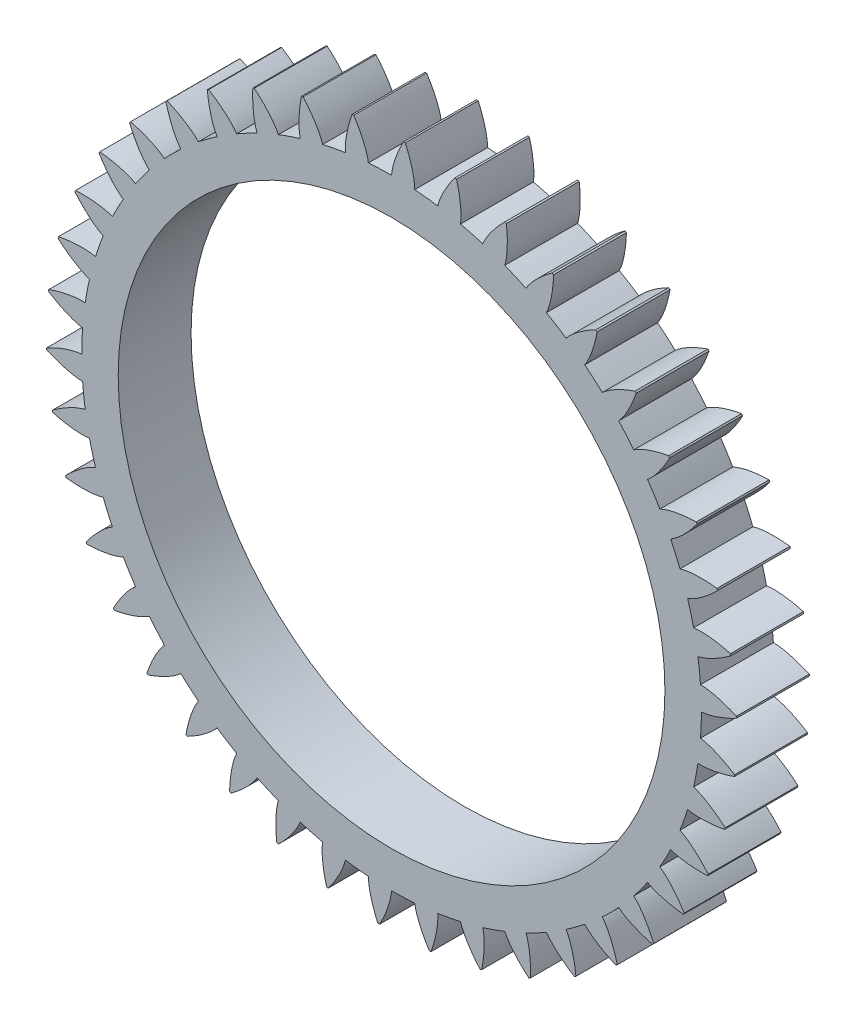
SolidWorks part; units mm, degrees
ref_plane "Front Plane" through (0, 0, 0) normal (0, 0, 1) x (1, 0, 0)
ref_plane "Top Plane" through (0, 0, 0) normal (0, 1, 0) x (1, 0, 0)
ref_plane "Right Plane" through (0, 0, 0) normal (1, 0, 0) x (0, 0, -1)
sketch "Sketch1" plane through (0, 0, 0) normal (0, 0, 1) x (1, 0, 0)
  line L0 (0, 0) -> (47.3193, -1.7706) construction
  line L1 (0, 0) -> (47.3193, 1.7706) construction
  line L2 (0, 0) -> (47.3193, -1.7706) construction
  line L3 (0, 0) -> (47.3524, 0) construction
  line L4 (0, 0) -> (47.0546, 5.3018) construction
  line L5 (0, 0) -> (47.3193, 1.7706)
  line L6 (42.4798, -1.5895) -> (37.4833, -1.4025)
  circle A0 centre (0, 0) radius 45.2 construction
  circle A1 centre (0, 0) radius 42.5095 construction
  circle A2 centre (0, 0) radius 42.4741 construction
  circle A3 centre (0, 0) radius 47.3524 construction
  arc A4 (42.5059, 0.5579) -> (42.4798, -1.5895) centre (0, 0) cw
  arc A5 (47.2632, 2.9041) -> (47.0335, -5.4865) centre (0, 0) cw
  arc A6 (37.4833, -1.4025) -> (37.4833, 1.4025) centre (0, 0) ccw
  spline S0 degree 4 poles (42.4741, 0) (42.5302, 0.0017) (42.6422, 0.0081) (42.9552, 0.0423) (43.546, 0.1494) (44.436, 0.3854) (45.6255, 0.8173) (47.1022, 1.5003) (48.755, 2.4501) (50.4757, 3.6438) (52.2195, 5.0775) (53.8537, 6.6343) (55.3803, 8.2963) (56.8717, 10.1359) (58.5748, 12.5231) (60.3856, 15.5166) (62.1816, 19.1625) (63.799, 23.3792) (65.0524, 27.7173) (65.9558, 32.1409) (66.5234, 36.6196) (66.7382, 40.5636) (66.7293, 43.9479) (66.5972, 46.7643) (66.4185, 49.0128) (66.1681, 51.2546) (65.8479, 53.487) (65.4591, 55.7094) (65.0607, 57.6414) (64.6778, 59.2907) (64.3799, 60.4692) (64.1876, 61.1947) (64.0217, 61.8024) (63.8414, 62.4443) (63.6884, 62.9728) (63.3886, 63.9768) (63.1489, 64.7323) (62.847, 65.6664) (62.5677, 66.4852) (62.2579, 67.3724) (61.953, 68.206) (61.7078, 68.8614) (61.5473, 69.276) (61.4636, 69.4921) knots 0 0 0 0 0 0.002802 0.005604 0.015718 0.02996 0.048734 0.068727 0.096889 0.125051 0.153212 0.181374 0.209535 0.237696 0.271429 0.327752 0.384075 0.440398 0.496721 0.553044 0.609367 0.66569 0.693852 0.722013 0.750174 0.778336 0.806497 0.834659 0.86282 0.876901 0.890982 0.895509 0.900036 0.909091 0.920455 0.931818 0.943182 0.954545 0.965909 0.977273 0.988636 1 1 1 1 1 construction
  spline S1 degree 4 poles (42.4741, 0) (42.5302, 0.0017) (42.6422, 0.0081) (42.9552, 0.0423) (43.546, 0.1494) (44.436, 0.3854) (45.6255, 0.8173) (47.1022, 1.5003) (48.755, 2.4501) (50.4757, 3.6438) (52.2195, 5.0775) (53.8537, 6.6343) (55.3803, 8.2963) (56.8717, 10.1359) (58.5748, 12.5231) (60.3856, 15.5166) (62.1816, 19.1625) (63.799, 23.3792) (65.0524, 27.7173) (65.9558, 32.1409) (66.5234, 36.6196) (66.7382, 40.5636) (66.7293, 43.9479) (66.5972, 46.7643) (66.4185, 49.0128) (66.1681, 51.2546) (65.8479, 53.487) (65.4591, 55.7094) (65.0607, 57.6414) (64.6778, 59.2907) (64.3799, 60.4692) (64.1876, 61.1947) (64.0217, 61.8024) (63.9109, 62.1968) (63.8419, 62.4392) (63.7962, 62.5976) knots 0 0 0 0 0 0.002802 0.005604 0.015718 0.02996 0.048734 0.068727 0.096889 0.125051 0.153212 0.181374 0.209535 0.237696 0.271429 0.327752 0.384075 0.440398 0.496721 0.553044 0.609367 0.66569 0.693852 0.722013 0.750174 0.778336 0.806497 0.834659 0.86282 0.876901 0.890982 0.895509 0.900036 0.909091 0.909091 0.909091 0.909091 0.909091
  dimension "pitchRadius" = 45.2
  dimension "addendumRadius" = 47.3524
  dimension "dedendumRadius" = 42.5095
  dimension "baseRadius" = 42.4741
  dimension "D1" = 4.286
  dimension "D2" = 2.143
  dimension "toothArc" = 8.571
  dimension "D3" = 5
extrude "Boss-Extrude1" add sketch "Sketch1" along normal blind 10 contours S1 A5 L5 A6 L6 A4 region at (41.1156, 0.2616, 0)
mirror "Mirror1" about plane through (0, 0, 10) normal (-0.0374, 0.9993, 0) of "Boss-Extrude1"
pattern_circular "CirPattern2" count 42 over 360 about axis through (0, 0, 10) along (0, 0, -1) of "Mirror1", "Boss-Extrude1"
equation "\"D1@Sketch1\"=\"toothArc@Sketch1\"/2"
equation "\"D2@Sketch1\"=\"toothArc@Sketch1\"/4"
equation "\"pitchRadius\"= 4.52"
equation "\"nTeeth\"= 42"
equation "\"pressureAngle\"= 20"
equation "\"baseRadius\"= \"pitchRadius\" * cos ( \"pressureAngle\" )"
equation "\"diametralPitch\"= \"nTeeth\" / ( 2 * \"pitchRadius\" )'note units: cm^-1"
equation "\"dedendum\"= 1.25 / \"diametralPitch\"'for full depth, 20 deg pressure angle"
equation "\"addendum\"= 1 / \"diametralPitch\""
equation "\"pitchRadius@Sketch1\"= \"pitchRadius\""
equation "\"addendumRadius@Sketch1\"= \"pitchRadius\" + \"addendum\""
equation "\"dedendumRadius@Sketch1\"= \"pitchRadius\" - \"dedendum\""
equation "\"baseRadius@Sketch1\"= \"baseRadius\""
equation "\"toothArc@Sketch1\"=360/\"nTeeth\""
